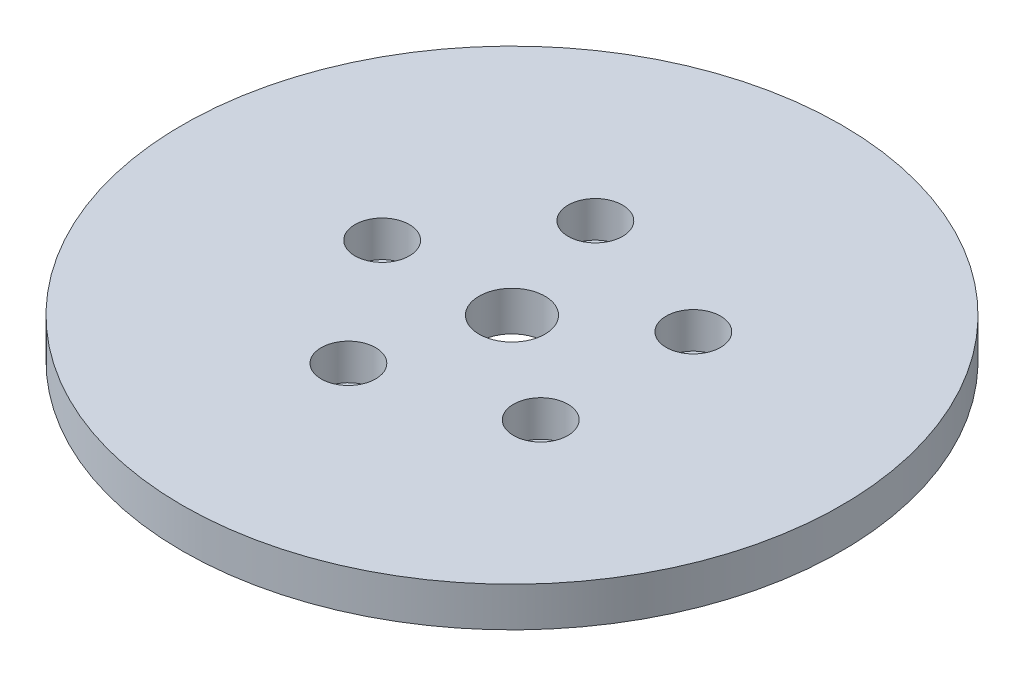
SolidWorks part; units mm, degrees
ref_plane "Front Plane" through (0, 0, 0) normal (0, 0, 1) x (1, 0, 0)
ref_plane "Top Plane" through (0, 0, 0) normal (0, 1, 0) x (1, 0, 0)
ref_plane "Right Plane" through (0, 0, 0) normal (1, 0, 0) x (0, 0, -1)
sketch "Sketch1" plane through (0, 0, 0) normal (0, 1, 0) x (1, 0, 0)
  circle A0 centre (0, 0) radius 100
  dimension "FLANGE_OD" = 200
extrude "Boss-Extrude1" add sketch "Sketch1" along normal blind 12
sketch "Sketch2" plane through (0, 0, 0) normal (0, 1, 0) x (1, 0, 0)
  circle A0 centre (0, 0) radius 10
  dimension "BORE_D" = 20
extrude "Cut-Extrude1" cut sketch "Sketch2" along normal through all
sketch "Sketch3" plane through (0, 12, 0) normal (0, 1, 0) x (1, 0, 0)
  circle A0 centre (0, 0) radius 39.3953 construction
  circle A1 centre (-39.3953, 0) radius 8.2492
  dimension "BOLT_D" = 16.4984
  dimension "BOLT_PCD" = 78.7906
extrude "Cut-Extrude2" cut sketch "Sketch3" against normal blind 10.9368
pattern_circular "CirPattern1" count 5 over 360 about axis through (0, 0, 0) along (0, 1, 0) of "Cut-Extrude2"
